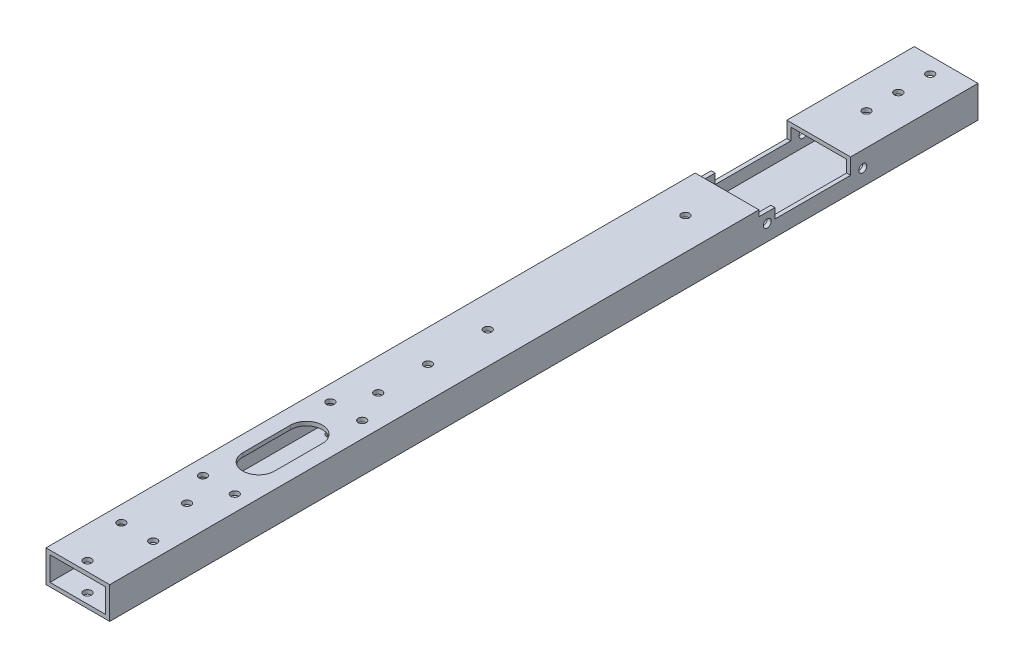
SolidWorks part; units mm, degrees
ref_plane "Front Plane" through (0, 0, 0) normal (0, 0, 1) x (1, 0, 0)
ref_plane "Top Plane" through (0, 0, 0) normal (0, 1, 0) x (1, 0, 0)
ref_plane "Right Plane" through (0, 0, 0) normal (1, 0, 0) x (0, 0, -1)
sketch "Sketch1" plane through (0, 0, 0) normal (0, 0, 1) x (1, 0, 0)
  line L1 (25.4, -12.7) -> (-25.4, -12.7)
  line L2 (25.4, -12.7) -> (25.4, 12.7)
  line L3 (25.4, 12.7) -> (-25.4, 12.7)
  line L4 (-25.4, -12.7) -> (-25.4, 12.7)
  line L5 (25.4, -12.7) -> (-25.4, 12.7) construction
  line L6 (25.4, 12.7) -> (-25.4, -12.7) construction
  line L7 (22.225, -9.525) -> (-22.225, -9.525)
  line L8 (22.225, -9.525) -> (22.225, 9.525)
  line L9 (22.225, 9.525) -> (-22.225, 9.525)
  line L10 (-22.225, -9.525) -> (-22.225, 9.525)
  line L11 (22.225, -9.525) -> (-22.225, 9.525) construction
  line L12 (22.225, 9.525) -> (-22.225, -9.525) construction
  point P0 (0, 0)
  point P6 (0, 0)
  dimension "D1" = 50.8
  dimension "D2" = 25.4
  dimension "D3" = 44.45
  dimension "D4" = 19.05
extrude "Boss-Extrude1" add sketch "Sketch1" along normal blind 692.15
sketch "Sketch2" plane through (25.4, 0, 0) normal (1, 0, 0) x (0, 0, -1)
  line L0 (-692.15, 12.7) -> (0, 12.7) construction
  line L1 (-161.925, 12.7) -> (-101.6, 12.7)
  line L2 (-161.925, 12.7) -> (-161.925, 0)
  line L3 (-161.925, 0) -> (-101.6, 0)
  line L4 (-101.6, 12.7) -> (-101.6, 0)
  line L6 (0, -12.7) -> (0, 12.7) construction
  dimension "D1" = 60.325
  dimension "D2" = 12.7
  dimension "D3" = 101.6
extrude "Cut-Extrude1" cut sketch "Sketch2" against normal through all
sketch "Sketch3" plane through (25.4, 0, 0) normal (1, 0, 0) x (0, 0, -1)
  line L0 (0, 0) -> (-133.147, 0) construction
  line L1 (-161.925, 0) -> (-161.925, 9.525) construction
  circle A0 centre (-167.9999, 0) radius 3.175
  circle A1 centre (-91.8139, 0) radius 3.175
  point P7 (-161.925, 4.7625)
  dimension "D1" = 6.35
  dimension "D2" = 6.35
  dimension "D3" = 6.0749
  dimension "D4" = 9.7861
extrude "Cut-Extrude2" cut sketch "Sketch3" against normal through all
sketch "Sketch4" plane through (25.4, 0, 0) normal (1, 0, 0) x (0, 0, -1)
  line L1 (-161.925, 12.7) -> (-174.625, 12.7)
  line L2 (-161.925, 12.7) -> (-161.925, 7.9375)
  line L3 (-161.925, 7.9375) -> (-174.625, 7.9375)
  line L4 (-174.625, 12.7) -> (-174.625, 7.9375)
  dimension "D1" = 4.7625
  dimension "D2" = 12.7
extrude "Cut-Extrude3" cut sketch "Sketch4" against normal through all
sketch "Sketch5" plane through (0, 12.7, 0) normal (0, 1, 0) x (1, 0, 0)
  line L0 (0, -174.625) -> (0, -692.15) construction
  line L1 (-25.4, -174.625) -> (25.4, -174.625) construction
  line L2 (25.4, -692.15) -> (-25.4, -692.15) construction
  line L3 (-25.4, -478.1591) -> (25.4, -478.1591) construction
  line L4 (-25.4, -692.15) -> (-25.4, -174.625) construction
  line L5 (22.225, -167.9999) -> (25.4, -167.9999) construction
  line L6 (25.4, -692.15) -> (25.4, -174.625) construction
  line L7 (-25.4, -579.7591) -> (25.4, -579.7591) construction
  line L8 (-25.4, -644.8067) -> (25.4, -644.8067) construction
  circle A0 centre (0, -207.8596) radius 3.175
  circle A1 centre (0, -365.4407) radius 3.175
  circle A2 centre (0, -413.1114) radius 3.175
  circle A3 centre (0, -452.7591) radius 3.175
  circle A4 centre (-12.7, -478.1591) radius 3.175
  circle A5 centre (12.7, -478.1591) radius 3.175
  circle A6 centre (-12.7, -579.7591) radius 3.175
  circle A7 centre (12.7, -579.7591) radius 3.175
  circle A8 centre (0, -605.1591) radius 3.175
  circle A9 centre (-12.7, -644.8067) radius 3.175
  circle A10 centre (12.7, -644.8067) radius 3.175
  circle A11 centre (0, -684.4543) radius 3.175
  circle A12 centre (0, -548.0091) radius 2.0828
  circle A13 centre (0, -535.3091) radius 2.0828
  circle A14 centre (0, -522.6091) radius 2.0828
  circle A15 centre (0, -509.9091) radius 2.0828
  dimension "D1" = 39.8597
  dimension "D2" = 157.5811
  dimension "D3" = 47.6707
  dimension "D4" = 39.6476
  dimension "D6" = 12.7
  dimension "D8" = 12.7
  dimension "D9" = 25.4
  dimension "D11" = 12.7
  dimension "D12" = 39.6476
  dimension "D13" = 4.1656
  dimension "D14" = 31.75
  dimension "D5" = 25.4
  dimension "D7" = 101.6
  dimension "D10" = 39.6476
  dimension "D15" = 4
extrude "Cut-Extrude4" cut sketch "Sketch5" against normal through all
sketch "Sketch7" plane through (0, 12.7, 0) normal (0, 1, 0) x (1, 0, 0)
  line L0 (0, -548.0091) -> (0, -509.9091) construction
  line L1 (-12.7, -548.0091) -> (-12.7, -509.9091)
  line L2 (12.7, -548.0091) -> (12.7, -509.9091)
  arc A0 (-12.7, -548.0091) -> (12.7, -548.0091) centre (0, -548.0091) ccw
  arc A1 (12.7, -509.9091) -> (-12.7, -509.9091) centre (0, -509.9091) ccw
  point P4 (0, -528.9591)
  dimension "D1" = 12.7
extrude "Cut-Extrude5" cut sketch "Sketch7" against normal blind 3.175
sketch "Sketch8" plane through (0, 12.7, 0) normal (0, 1, 0) x (1, 0, 0)
  line L0 (0, -101.6) -> (0, 0) construction
  line L1 (-25.4, -101.6) -> (25.4, -101.6) construction
  circle A0 centre (0, -12.7) radius 3.175
  circle A1 centre (0, -38.1) radius 3.175
  circle A2 centre (0, -63.5) radius 3.175
  dimension "D1" = 6.35
  dimension "D2" = 12.7
  dimension "D3" = 3
extrude "Cut-Extrude6" cut sketch "Sketch8" against normal through all
sketch "Sketch9" plane through (0, 12.7, 0) normal (0, 1, 0) x (1, 0, 0)
  line L0 (-25.4, -692.15) -> (-25.4, -174.625) construction
  line L1 (25.4, -692.15) -> (-25.4, -692.15)
  line L2 (25.4, -692.15) -> (25.4, -595.0297)
  line L3 (25.4, -595.0297) -> (-25.4, -595.0297)
  line L4 (-25.4, -692.15) -> (-25.4, -595.0297)
  dimension "D1" = 97.1203
extrude "Cut-Extrude7" [suppressed] cut sketch "Sketch9" against normal through all
